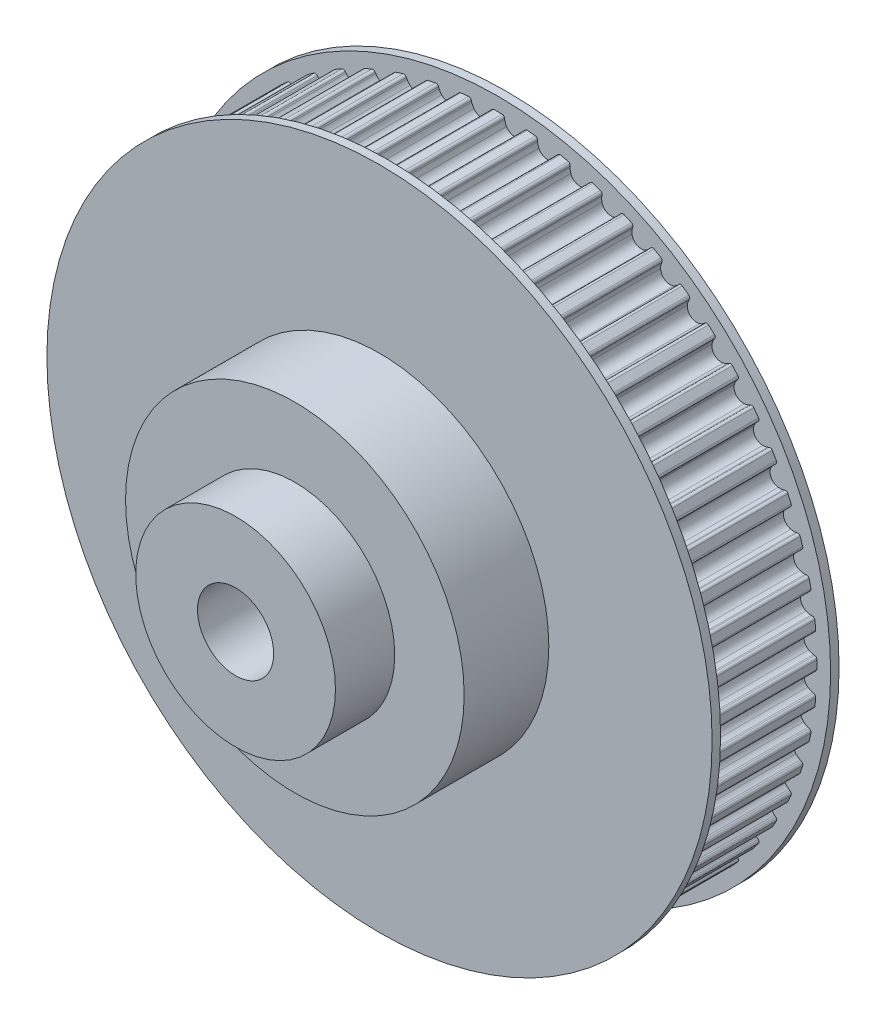
SolidWorks part; units mm, degrees
note: '?' marks a value the reader was unsure of.
material "PET"
ref_plane "Front Plane" through (0, 0, 0) normal (0, 0, 1) x (1, 0, 0)
ref_plane "Top Plane" through (0, 0, 0) normal (0, 1, 0) x (1, 0, 0)
ref_plane "Right Plane" through (0, 0, 0) normal (1, 0, 0) x (0, 0, -1)
sketch "Sketch1" plane through (0, 0, 0) normal (0, 0, 1) x (1, 0, 0)
  line L0 (0, 0) -> (0, 19.0986) construction
  line L1 (0, 0) -> (0.9995, 19.0724) construction
  line L2 (0, 0) -> (1.3987, 19.0473) construction
  circle A0 centre (0, 0) radius 19.0986 construction
  circle A1 centre (0, 0) radius 18.0946 construction
  circle A2 centre (0, 0) radius 18.8446 construction
  arc A3 (0.947, 18.0698) -> (0.4969, 18.3439) centre (0.976, 18.624) cw
  arc A4 (0.3947, 18.624) -> (0.384, 18.7063) centre (1.3801, 18.794) cw
  circle A5 centre (0, 0) radius 18.6946 construction
  arc A6 (-0.2365, 18.8431) -> (0.2365, 18.8431) centre (0, 0) cw
  arc A7 (0.2365, 18.8431) -> (0.384, 18.7063) centre (0.2346, 18.6931) cw
  arc A8 (0.3947, 18.624) -> (0.4969, 18.3439) centre (1.2192, 18.7662) ccw
  arc A9 (-0.947, 18.0698) -> (-0.4969, 18.3439) centre (-0.976, 18.624) ccw
  arc A10 (-0.3947, 18.624) -> (-0.4969, 18.3439) centre (-1.2192, 18.7662) cw
  arc A11 (-0.3947, 18.624) -> (-0.384, 18.7063) centre (-1.3801, 18.794) ccw
  arc A12 (-0.2365, 18.8431) -> (-0.384, 18.7063) centre (-0.2346, 18.6931) ccw
  arc A13 (-0.947, 18.0698) -> (0.947, 18.0698) centre (0, 0) cw
  dimension "D1" = 38.1972
  dimension "D6" = 0.555
  dimension "D7" = 1
  dimension "D9" = 0.15
  dimension "D2" = 3
  dimension "D3" = 1.2
  dimension "D4" = 1.004
  dimension "D5" = 0.75
  dimension "D8" = 0.15
extrude "Boss-Extrude1" add sketch "Sketch1" along normal blind 6.5
ref_axis "Axis1" through (0, 0, -0.375) along (0, 0, 1)?
pattern_circular "CirPattern1" count 60 over 360 about axis through (0, 0, 0) along (0, 0, 1) of bodies 107
sketch "Sketch2" plane through (0, 0, 0) normal (0, 0, -1) x (-1, 0, 0)
  circle A0 centre (0, 0) radius 18.0946
  arc A1 (0.947, 18.0698) -> (-0.947, 18.0698) centre (0, 0) ccw construction
extrude "Boss-Extrude2" add sketch "Sketch2" against normal up to surface (6.5 mm away)
sketch "Schizzo1" plane through (0, 0, 6.5) normal (0, 0, 1) x (1, 0, 0)
  circle A0 centre (0, 0) radius 19.6446
  arc A1 (-9.2168, 16.4368) -> (-9.6263, 16.2004) centre (0, 0) ccw construction
  dimension "D1" = 0.8
extrude "Estrusione-Estrusione1" add sketch "Schizzo1" along normal blind 0.5
ref_plane "Piano1" through (0, 0, 3.25) normal (0, 0, -1) x (-1, 0, 0)
mirror "Specchia1" about plane through (0, 0, 3.25) normal (0, 0, -1) of "Estrusione-Estrusione1"
sketch "Schizzo2" plane through (0, 0, 7) normal (0, 0, 1) x (1, 0, 0)
  circle A0 centre (0, 0) radius 5.9
  dimension "D1" = 11.8
extrude "Estrusione-Estrusione2" add sketch "Schizzo2" along normal blind 8.5
sketch "Schizzo3" plane through (0, 0, -0.5) normal (0, 0, -1) x (-1, 0, 0)
  circle A0 centre (0, 0) radius 2.25
  point P0 (0, 0)
  dimension "D1" = 4.5
extrude "Taglio-Estrusione1" cut sketch "Schizzo3" against normal through all
sketch "Schizzo5" plane through (0, 0, -0.5) normal (0, 0, -1) x (-1, 0, 0)
  circle A0 centre (0, 0) radius 5
  dimension "D1" = 10
extrude "Taglio-Estrusione2" cut sketch "Schizzo5" against normal blind 3
sketch "Schizzo6" plane through (0, 0, 7) normal (0, 0, 1) x (1, 0, 0)
  circle A0 centre (0, 0) radius 10
  dimension "D1" = 20
extrude "Estrusione-Estrusione3" add sketch "Schizzo6" along normal blind 5
equation "\"NumTeeth\"= 60'The number of teeth that the pulley has"
equation "\"ToothPitch\"= 2.00mm'Distance between 2 teeth"
equation "\"PulleyDia\"= \"NumTeeth\" * \"ToothPitch\" / PI"
equation "\"ToothAng\"= ( 360deg / \"NumTeeth\" ) * 1deg"
equation "\"TransOffsetAngle\"= \"ToothAng\" * .2deg"
equation "\"ShoulderRad\"= 0.15mm"
equation "\"RootRad\"= 0.555mm"
equation "\"TransRad\"= 1mm"
equation "\"ToothHeight\"= 0.75mm"
equation "\"PLD\"= 0.254mm"
equation "\"D1@CirPattern1\"=\"NumTeeth\""
equation "\"D1@Sketch1\"=\"PulleyDia\""
equation "\"D7@Sketch1\"=\"TransRad\""
equation "\"D9@Sketch1\"=\"ShoulderRad\""
equation "\"D6@Sketch1\"=\"RootRad\""
equation "\"D3@Sketch1\"=\"TransOffsetAngle\""
equation "\"D5@Sketch1\"=\"ToothHeight\""
equation "\"D2@Sketch1\"=\"ToothAng\"/2"
equation "\"D4@Sketch1\"=\"PLD\"+\"ToothHeight\""
equation "\"D8@Sketch1\"=\"ShoulderRad\""
equation "\"altezza\"= 6.5mm"
equation "\"D1@Boss-Extrude1\"=\"altezza\""
